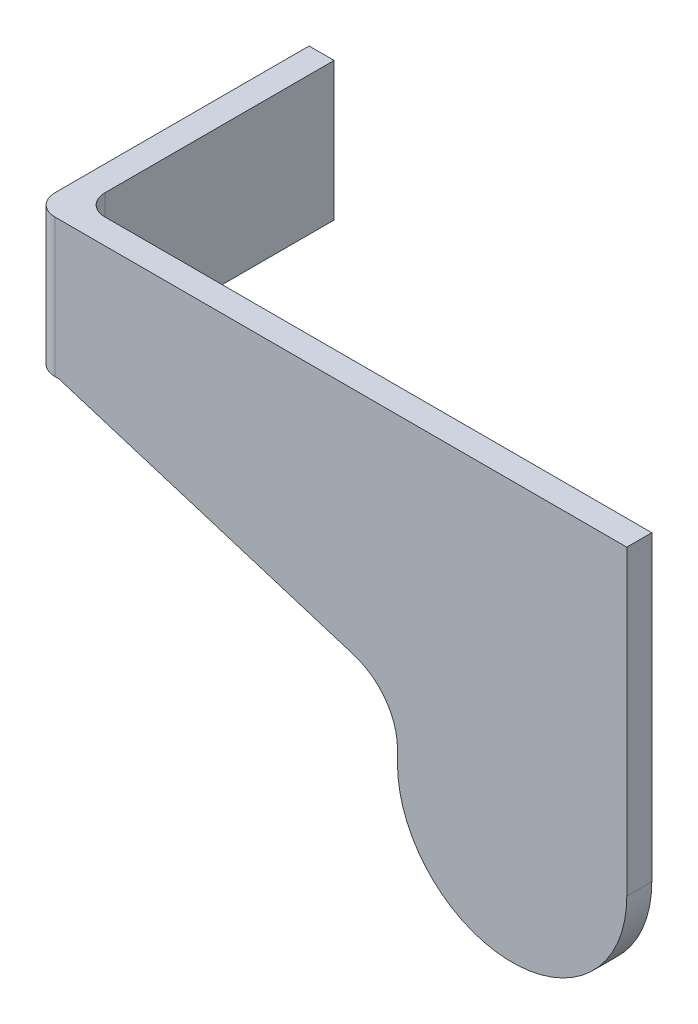
SolidWorks part; units mm, degrees
ref_plane "Piano frontale" through (0, 0, 0) normal (0, 0, 1) x (1, 0, 0)
ref_plane "Piano superiore" through (0, 0, 0) normal (0, 1, 0) x (1, 0, 0)
ref_plane "Piano destro" through (0, 0, 0) normal (1, 0, 0) x (0, 0, -1)
sketch "Schizzo2" plane through (0, 0, 0) normal (0, 0, 1) x (1, 0, 0)
  line L0 (0, 0) -> (0, 45) construction
  line L1 (-27.5, 0) -> (-27.5, 45)
  line L2 (27.5, 0) -> (27.5, 45)
  arc A0 (-27.5, 0) -> (27.5, 0) centre (0, 0) ccw
  arc A1 (27.5, 45) -> (-27.5, 45) centre (0, 45) ccw
  point P3 (0, 22.5)
  point P8 (0, -27.5)
  point P9 (0, 72.5)
  dimension "D1" = 100
  dimension "D2" = 55
extrude "Estrusione-Estrusione1" add sketch "Schizzo2" along normal blind 6
sketch "Schizzo3" plane through (0, 0, 0) normal (0, 0, 1) x (1, 0, 0)
  line L1 (27.5, 0) -> (-108.7, 0)
  line L2 (27.5, 0) -> (27.5, 72.5)
  line L3 (27.5, 72.5) -> (-108.7, 72.5)
  line L4 (-108.7, 0) -> (-108.7, 72.5)
  arc A0 (27.5, 45) -> (-27.5, 45) centre (0, 45) ccw construction
  point P9 (0, 72.5)
  dimension "D1" = 136.2
  dimension "D2" = 72.5
  dimension "D3" = 72.5
extrude "Estrusione-Estrusione2" add sketch "Schizzo3" along normal blind 6
sketch "Schizzo4" plane through (0, 0, 6) normal (0, 0, 1) x (1, 0, 0)
  line L2 (-27.5, 0) -> (-108.7, 0)
  line L3 (-108.7, 0) -> (-108.7, 39.3472)
  line L4 (-108.7, 39.3472) -> (-27.5, 14.1424)
  line L5 (-27.5, 14.1424) -> (-27.5, 0)
  line L6 (-108.7, 72.5) -> (-108.7, 0) construction
extrude "Taglio-Estrusione1" cut sketch "Schizzo4" against normal through all
fillet "Raccordo5" radius 15 1 edges at (-27.5, 14.1424, 3) type face fillet first side face at (-68.1, 26.7448, 3) second side face at (0, -13.75, 3) second side face at (-27.5, 7.0712, 3)
sketch "Schizzo9" plane through (0, 0, 0) normal (0, 0, 1) x (1, 0, 0)
  line L0 (-108.7, 39.3472) -> (-114.7, 39.3472)
  line L1 (-114.7, 39.3472) -> (-114.7, 72.5)
  line L2 (-114.7, 72.5) -> (-108.7, 72.5)
  line L3 (-108.7, 72.5) -> (-108.7, 39.3472)
extrude "Estrusione-Estrusione5" add sketch "Schizzo9" against normal blind 60 and the other way up to vertex (6 mm away) other way up to point (-108.7, 72.5, 6)
fillet "Raccordo6" radius 5 1 edges at (-108.7, 55.9236, 0) type face fillet first side face at (-36.1571, 25.5845, 0) second side face at (-108.7, 55.9236, -30)
fillet "Raccordo7" radius 5 1 edges at (-114.7, 55.9236, 6)
